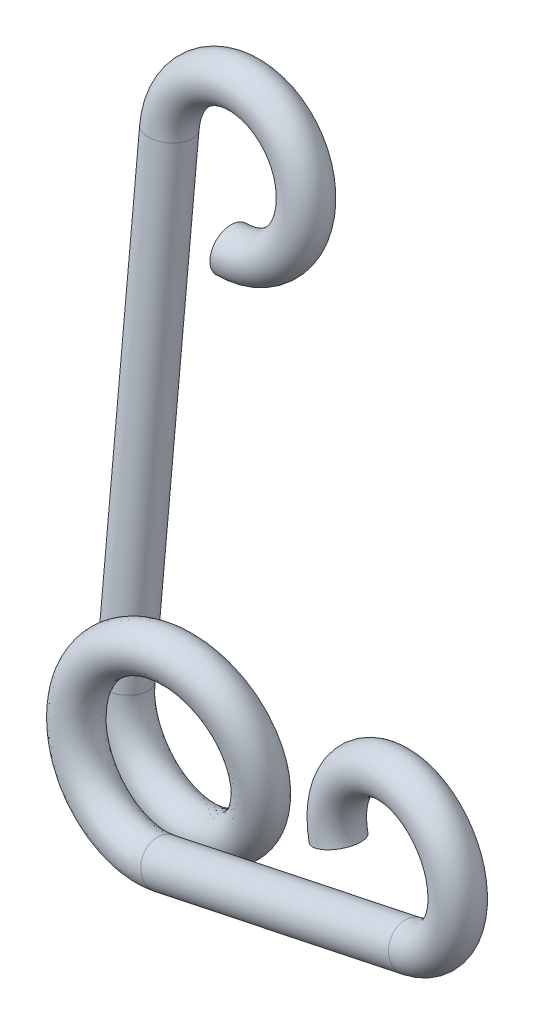
SolidWorks part; units mm, degrees
note: '?' marks a value the reader was unsure of.
ref_plane "Front Plane" through (0, 0, 0) normal (0, 0, 1) x (1, 0, 0)
ref_plane "Top Plane" through (0, 0, 0) normal (0, 1, 0) x (1, 0, 0)
ref_plane "Right Plane" through (0, 0, 0) normal (1, 0, 0) x (0, 0, -1)
sketch "Sketch1" plane through (0, 0, 0) normal (0, 0, 1) x (1, 0, 0)
  circle A0 centre (0, 0) radius 2.925
  dimension "D1" = 5.85
curve "Helix/Spiral1" pitch 1.7792 height 2.304 radius 2.925 centre (0, 0, 0) axis (0, 0, 1) start towards (1, 0, 0)
sweep "Sweep1" add path "Helix/Spiral1" circular profile diameter 1.544 parameters "D3"=1.544
sketch "Sketch7" plane through (0, 0, 0) normal (0, 0.9953, -0.0964) x (1, 0, 0)
  line L0 (-3.697, 0) -> (-2.153, 0) construction
  circle A0 centre (-2.925, 0) radius 0.772 construction
  circle A1 centre (-2.925, 0) radius 0.772
extrude "Boss-Extrude1" add sketch "Sketch7" along normal blind 16.8
sketch "Sketch8" plane through (0.2122, 0.0616, 0.0214) normal (0.9559, 0.2774, 0.0964) x (0.1075, -0.0253, -0.9939)
  line L0 (-2.1315, -3.8171) -> (-2.1315, -2.2731) construction
  circle A0 centre (-2.1315, -3.0451) radius 0.772 construction
  circle A1 centre (-2.1315, -3.0451) radius 0.772
extrude "Boss-Extrude2" add sketch "Sketch8" along normal blind 10.57
ref_axis "Axis1" through (-2.925, 16.5666, -1.6038) along (0, -0.9953, 0.0964)?
ref_plane "Plane1" through (0, 0, 0) normal (0, 0.0964, 0.9953) x (1, 0, 0)
ref_axis "Axis2" through (11.3938, 0.2608, 3.3706) along (-0.9559, -0.2774, -0.0964)?
ref_plane "Plane2" through (-0.2292, 0.0539, 2.1184) normal (0.1075, -0.0253, -0.9939) x (-0.9942, -0.0023, -0.1075)
sketch "Sketch10" plane through (0, 0, 0) normal (0, 0.0964, 0.9953) x (1, 0, 0)
  line L0 (-2.153, 16.8) -> (-3.697, 16.8) construction
  line L1 (-2.153, 16.8) -> (-3.697, 16.8) construction
  line L2 (-2.925, 16.8) -> (-0.425, 16.8) construction
  line L3 (-0.425, 16.8) -> (-0.425, 14.3) construction
  line L6 (-2.925, 16.644) -> (-2.925, 0.156) construction
  arc A0 (-2.925, 16.8) -> (-0.425, 14.3) centre (-0.425, 16.8) cw
  dimension "D2" = 2.5
  dimension "D1" = 90
sketch "Sketch11" plane through (0, 16.7218, -1.6188) normal (0, 0.9953, -0.0964) x (1, 0, 0)
  circle A0 centre (-2.925, 0) radius 0.772 construction
  circle A1 centre (-2.925, 0) radius 0.772
sweep "Sweep2" add profiles "Sketch11" path "Sketch10"
sketch "Sketch12" plane through (-0.2292, 0.0539, 2.1184) normal (0.1075, -0.0253, -0.9939) x (-0.9942, -0.0023, -0.1075)
  line L0 (-11.0008, 0.7856) -> (-11.4259, -0.6988) construction
  line L1 (-11.0008, 0.7856) -> (-11.4259, -0.6988) construction
  line L2 (-11.0008, 0.7856) -> (-10.5251, 2.4468) construction
  line L3 (-10.5251, 2.4468) -> (-8.1217, 1.7586) construction
  line L5 (-11.6907, 0.1801) -> (-0.554, -3.0089) construction
  arc A0 (-11.2133, 0.0434) -> (-8.1217, 1.7586) centre (-10.5251, 2.4468) cw
  dimension "D2" = 2.5
  dimension "D1" = 90
sketch "Sketch13" plane through (10.3162, 2.9938, 1.0399) normal (0.9559, 0.2774, 0.0964) x (0.1075, -0.0253, -0.9939)
  circle A0 centre (-2.1315, -3.0451) radius 0.772 construction
  circle A1 centre (-2.1315, -3.0451) radius 0.772
sweep "Sweep3" add profiles "Sketch13" path "Sketch12"
equation "\"D_coil\"=0.005850"
equation "\"d_wire\"=0.001544"
equation "\"Nb\"=1.294954"
equation "\"loop_diam\"=0.005000"
equation "\"height\"=0.002304"
equation "\"l_i_arm\"=0.010570"
equation "\"l_p_arm\"=0.016800"
equation "\"D1@Sketch1\"=\"D_coil\"*1000"
equation "\"D3@Helix/Spiral1\"=\"height\"*1000"
equation "\"D5@Helix/Spiral1\"=\"Nb\""
equation "\"D3@Sweep1\"=\"d_wire\"*1000"
equation "\"D1@Boss-Extrude1\"=\"l_p_arm\"*1000"
equation "\"D1@Boss-Extrude2\"=\"l_i_arm\"*1000"
equation "\"D2@Sketch10\"=\"loop_diam\"*1000/2"
equation "\"D2@Sketch12\"=\"loop_diam\"*1000/2"
